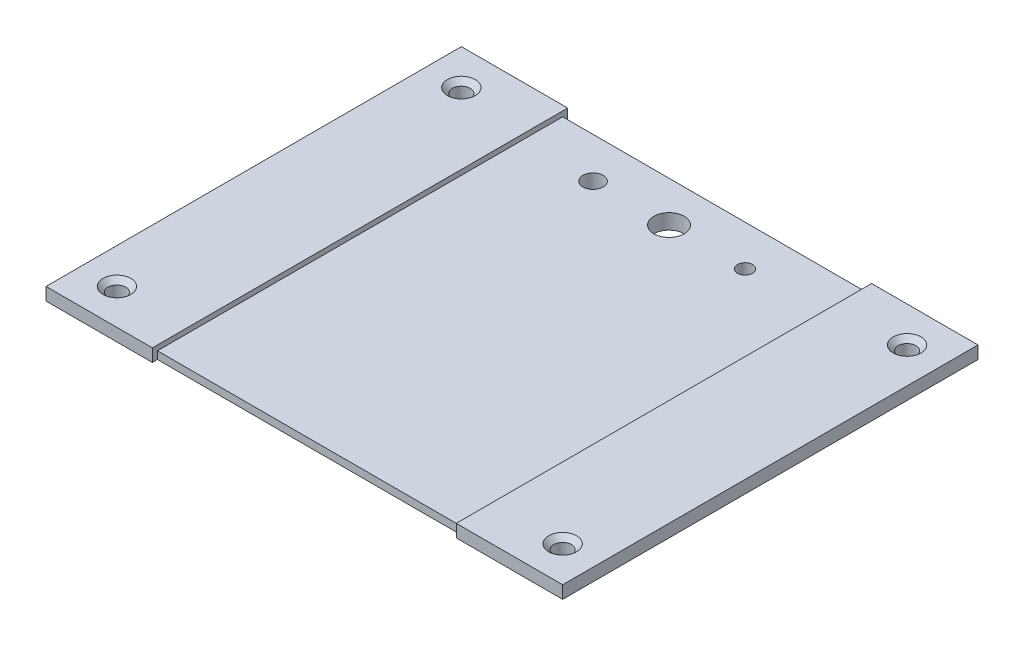
SolidWorks part; units mm, degrees
ref_plane "Plan de face" through (0, 0, 0) normal (0, 0, 1) x (1, 0, 0)
ref_plane "Plan de dessus" through (0, 0, 0) normal (0, 1, 0) x (1, 0, 0)
ref_plane "Plan de droite" through (0, 0, 0) normal (1, 0, 0) x (0, 0, -1)
sketch "Esquisse1" plane through (0, 0, 0) normal (0, 1, 0) x (1, 0, 0)
  line L1 (0, 0) -> (102, 0)
  line L2 (0, 0) -> (0, 80)
  line L3 (0, 80) -> (102, 80)
  line L4 (102, 0) -> (102, 80)
  dimension "D1" = 102
  dimension "D2" = 80
extrude "Boss.-Extru.1" add sketch "Esquisse1" along normal blind 1.5
sketch "Esquisse2" plane through (0, 0, 0) normal (0, -1, 0) x (1, 0, 0)
  line L0 (0, 0) -> (102, 0) construction
  line L1 (3, -2) -> (99, -2)
  line L2 (3, -2) -> (3, -78)
  line L3 (3, -78) -> (99, -78)
  line L4 (99, -2) -> (99, -78)
  line L5 (0, -80) -> (0, 0) construction
  line L6 (102, 0) -> (102, -80) construction
  line L7 (102, -80) -> (0, -80) construction
  dimension "D1" = 2
  dimension "D2" = 3
  dimension "D3" = 3
  dimension "D4" = 2
extrude "Boss.-Extru.2" add sketch "Esquisse2" along normal blind 1.5
sketch "Esquisse3" plane through (0, 1.5, 0) normal (0, 1, 0) x (1, 0, 0)
  line L0 (0, 0) -> (102, 0) construction
  line L1 (0, 80) -> (0, 0) construction
  line L2 (102, 80) -> (0, 80) construction
  line L3 (102, 0) -> (102, 80) construction
  circle A0 centre (7, 74) radius 1.75
  circle A1 centre (7, 6) radius 1.75
  circle A2 centre (95, 6) radius 1.75
  circle A3 centre (95, 74) radius 1.75
  circle A4 centre (35, 72) radius 2
  circle A5 centre (50, 72) radius 3
  circle A6 centre (65, 72) radius 1.5
  dimension "D1" = 3.5
  dimension "D2" = 3.5
  dimension "D3" = 3.5
  dimension "D4" = 3.5
  dimension "D5" = 6
  dimension "D6" = 7
  dimension "D7" = 7
  dimension "D8" = 6
  dimension "D9" = 6
  dimension "D10" = 7
  dimension "D12" = 6
  dimension "D13" = 4
  dimension "D14" = 6
  dimension "D15" = 3
  dimension "D16" = 8
  dimension "D17" = 8
  dimension "D18" = 8
  dimension "D19" = 15
  dimension "D20" = 15
  dimension "D21" = 35
  dimension "D11" = 7
extrude "Enlèv. mat.-Extru.1" cut sketch "Esquisse3" against normal blind 5
sketch "Esquisse6" plane through (0, 1.5, 0) normal (0, 1, 0) x (1, 0, 0)
  line L4 (0, 0) -> (102, 0) construction
  line L5 (102, 80) -> (81, 80)
  line L6 (102, 80) -> (102, 0)
  line L7 (102, 0) -> (81, 0)
  line L8 (81, 80) -> (81, 0)
  line L10 (0, 80) -> (21, 80)
  line L11 (0, 80) -> (0, 0)
  line L12 (0, 0) -> (21, 0)
  line L13 (21, 80) -> (21, 0)
  circle A0 centre (7, 74) radius 1.75
  circle A1 centre (7, 6) radius 1.75
  circle A2 centre (95, 6) radius 1.75
  circle A3 centre (95, 74) radius 1.75
  dimension "D1" = 3.5
  dimension "D2" = 3.5
  dimension "D3" = 3.5
  dimension "D4" = 3.5
  dimension "D5" = 21
  dimension "D6" = 21
extrude "Boss.-Extru.5" add sketch "Esquisse6" along normal blind 1
chamfer "Chanfrein2" distance 1 angle 45 4 edges at (7, 2.5, -72.25) (7, 2.5, -4.25) (95, 2.5, -4.25) (95, 2.5, -72.25)
sketch "Esquisse7" plane through (0, 0, 0) normal (0, 0, 1) x (1, 0, 0)
  line L0 (0, 0) -> (102, 0) construction
  line L1 (0, 2.5) -> (21, 2.5)
  line L2 (0, 2.5) -> (0, 0)
  line L3 (0, 0) -> (21, 0)
  line L4 (21, 2.5) -> (21, 0)
  line L6 (102, 2.5) -> (81, 2.5)
  line L7 (102, 2.5) -> (102, 0)
  line L8 (102, 0) -> (81, 0)
  line L9 (81, 2.5) -> (81, 0)
extrude "Boss.-Extru.6" add sketch "Esquisse7" along normal blind 1
sketch "Esquisse8" plane through (0, 0, -80) normal (0, 0, -1) x (-1, 0, 0)
  line L1 (-81, 2.5) -> (-102, 2.5)
  line L2 (-81, 2.5) -> (-81, 0)
  line L3 (-81, 0) -> (-102, 0)
  line L4 (-102, 2.5) -> (-102, 0)
  line L5 (-21, 2.5) -> (0, 2.5)
  line L6 (-21, 2.5) -> (-21, 0)
  line L7 (-21, 0) -> (0, 0)
  line L8 (0, 2.5) -> (0, 0)
extrude "Boss.-Extru.7" add sketch "Esquisse8" along normal blind 1
